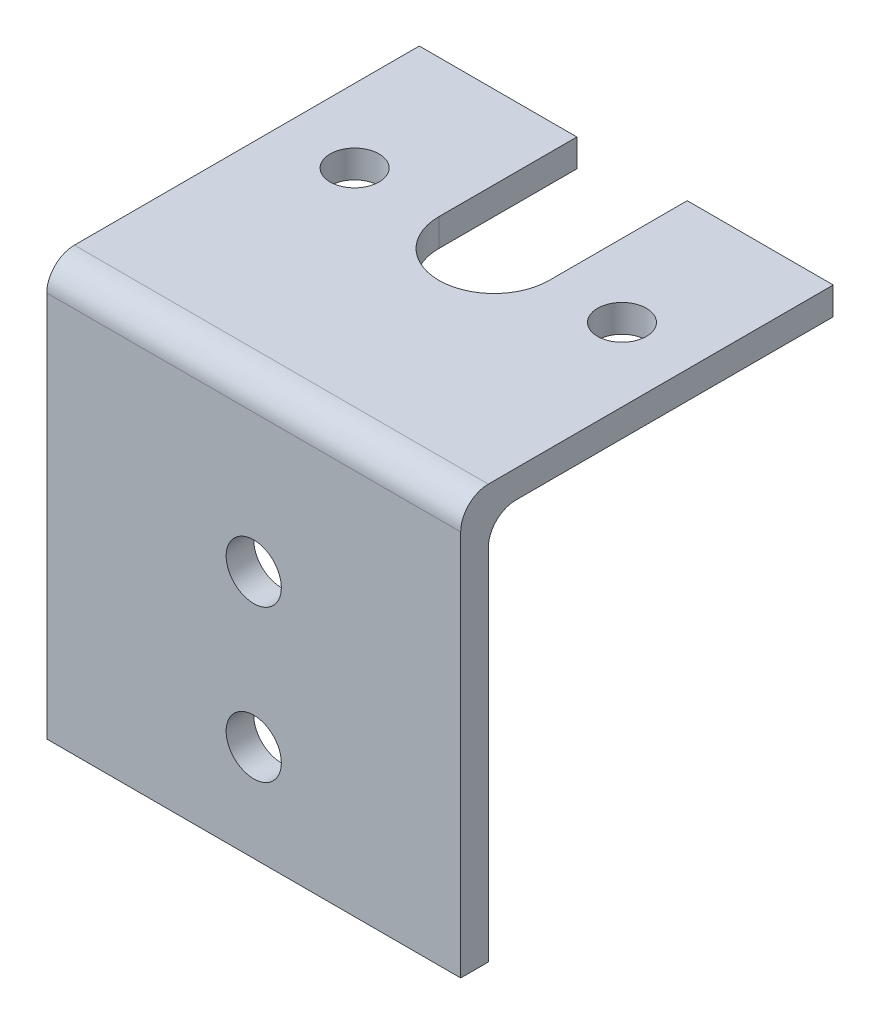
SolidWorks part; units mm, degrees
ref_plane "Front Plane" through (0, 0, 0) normal (0, 0, 1) x (1, 0, 0)
ref_plane "Top Plane" through (0, 0, 0) normal (0, 1, 0) x (1, 0, 0)
ref_plane "Right Plane" through (0, 0, 0) normal (1, 0, 0) x (0, 0, -1)
sketch "Sketch1" plane through (0, 0, 0) normal (0, 1, 0) x (1, 0, 0)
  line L0 (-19.5834, -8.6292) -> (18.5166, -8.6292) construction
  line L1 (-19.5834, 16.7708) -> (-5.08, 16.7708)
  line L2 (-19.5834, 16.7708) -> (-19.5834, -14.9792)
  line L3 (-19.5834, -14.9792) -> (18.5166, -14.9792)
  line L4 (18.5166, 16.7708) -> (18.5166, -14.9792)
  line L5 (-19.5834, 4.0708) -> (18.5166, 4.0708) construction
  line L10 (-5.08, -1.0092) -> (-5.08, 16.7708)
  line L11 (5.08, -1.0092) -> (5.08, 16.7708)
  line L12 (5.08, 16.7708) -> (18.5166, 16.7708)
  line L13 (-5.08, -1.0092) -> (5.08, -1.0092)
  circle A1 centre (-12.8397, 4.0708) radius 2.2479
  circle A2 centre (11.7729, 4.0708) radius 2.2479
  point P13 (-12.4536, 4.0708)
  point P14 (11.7729, 4.0708)
  dimension "D1" = 25.4
  dimension "D4" = 4.4958
  dimension "D5" = 4.4958
  dimension "D2" = 38.1
  dimension "D3" = 31.75
  dimension "D6" = 6.7437
  dimension "D7" = 6.7437
  dimension "D8" = 10.16
  dimension "D9" = 12.7
  dimension "D10" = 5.08
extrude "Boss-Extrude1" add sketch "Sketch1" along normal blind 2.54
fillet "Fillet1" radius 5.08 2 edges at (5.08, 1.27, 1.0092) (-5.08, 1.27, 1.0092)
sketch "Sketch2" plane through (0, 0, 14.9792) normal (0, 0, 1) x (1, 0, 0)
  line L0 (18.5166, 2.54) -> (18.5166, 0) construction
  line L1 (-19.5834, 2.54) -> (18.5166, 2.54)
  line L2 (-19.5834, 2.54) -> (-19.5834, -35.56)
  line L3 (-19.5834, -35.56) -> (18.5166, -35.56)
  line L4 (18.5166, 2.54) -> (18.5166, -35.56)
  line L5 (-0.5334, 2.54) -> (-0.5334, -35.56) construction
  circle A0 centre (-0.5334, -12.7) radius 2.54
  circle A1 centre (-0.5334, -26.67) radius 2.54
  point P13 (0, 0)
  dimension "D2" = 5.08
  dimension "D3" = 5.08
  dimension "D1" = 38.1
  dimension "D4" = 13.97
  dimension "D5" = 15.24
extrude "Boss-Extrude2" add sketch "Sketch2" along normal blind 2.54
fillet "Fillet2" radius 2.54 1 edges at (-0.5334, 0, 14.9792)
fillet "Fillet3" radius 2.54 1 edges at (-0.5334, 2.54, 17.5192)
